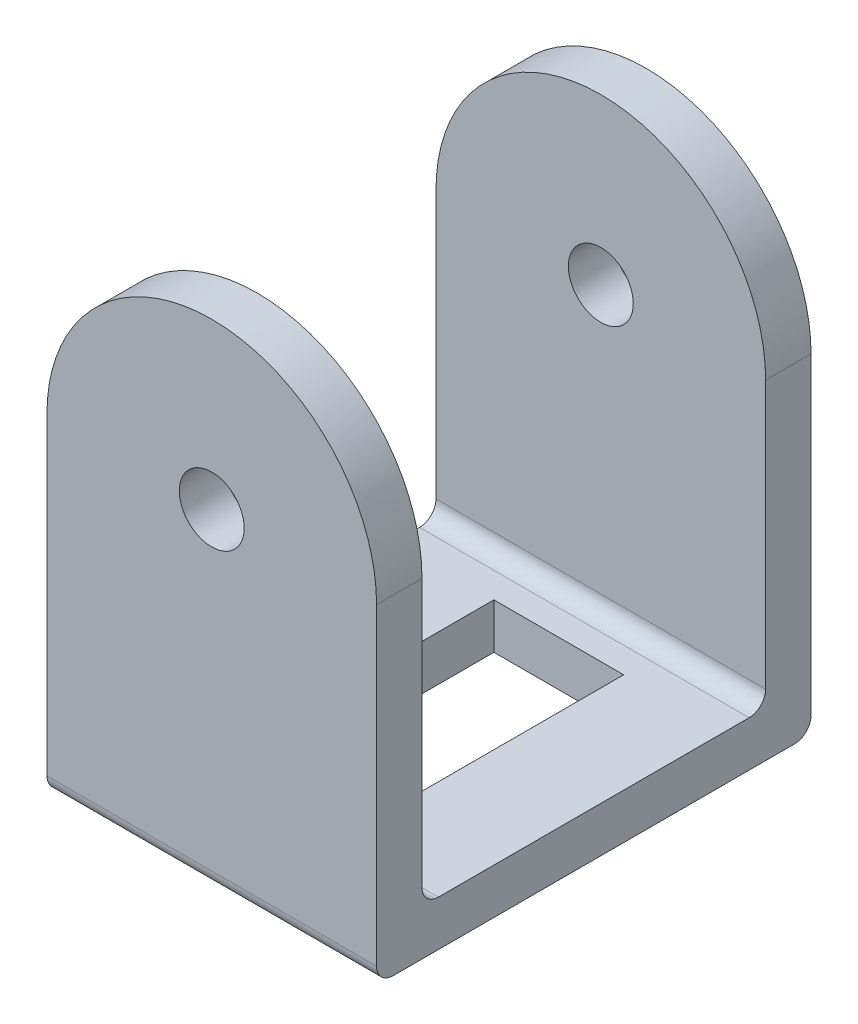
SolidWorks part; units mm, degrees
material "PBT General Purpose"
ref_plane "Front Plane" through (0, 0, 0) normal (0, 0, 1) x (1, 0, 0)
ref_plane "Top Plane" through (0, 0, 0) normal (0, 1, 0) x (1, 0, 0)
ref_plane "Right Plane" through (0, 0, 0) normal (1, 0, 0) x (0, 0, -1)
sketch "Sketch1" plane through (0, 0, 0) normal (0, 1, 0) x (1, 0, 0)
  line L1 (25.4, -33.48) -> (-25.4, -33.48)
  line L2 (25.4, -33.48) -> (25.4, 33.48)
  line L3 (25.4, 33.48) -> (-25.4, 33.48)
  line L4 (-25.4, -33.48) -> (-25.4, 33.48)
  line L5 (25.4, -33.48) -> (-25.4, 33.48) construction
  line L6 (25.4, 33.48) -> (-25.4, -33.48) construction
  point P0 (0, 0)
  dimension "D1" = 50.8
  dimension "D2" = 66.96
extrude "Boss-Extrude1" add sketch "Sketch1" along normal blind 7
sketch "Sketch2" plane through (0, 7, 0) normal (0, 1, 0) x (1, 0, 0)
  line L1 (10, -20) -> (-10, -20)
  line L2 (10, -20) -> (10, 20)
  line L3 (10, 20) -> (-10, 20)
  line L4 (-10, -20) -> (-10, 20)
  line L5 (10, -20) -> (-10, 20) construction
  line L6 (10, 20) -> (-10, -20) construction
  point P0 (0, 0)
  dimension "D1" = 20
  dimension "D2" = 40
extrude "Cut-Extrude1" cut sketch "Sketch2" against normal blind 7
sketch "Sketch3" plane through (0, 7, 0) normal (0, 1, 0) x (1, 0, 0)
  line L0 (25.4, -33.48) -> (25.4, 33.48) construction
  line L1 (-25.4, 33.48) -> (25.4, 33.48)
  line L2 (-25.4, 33.48) -> (-25.4, 26.48)
  line L3 (-25.4, 26.48) -> (25.4, 26.48)
  line L4 (25.4, 33.48) -> (25.4, 26.48)
  line L5 (-25.4, 33.48) -> (-25.4, -33.48) construction
  line L6 (25.4, -33.48) -> (-25.4, -33.48)
  line L7 (25.4, -33.48) -> (25.4, -26.48)
  line L8 (25.4, -26.48) -> (-25.4, -26.48)
  line L9 (-25.4, -33.48) -> (-25.4, -26.48)
  dimension "D1" = 7
  dimension "D2" = 7
extrude "Boss-Extrude2" add sketch "Sketch3" along normal blind 69.2
fillet "Fillet2" 2 edges at (-25.4, 76.2, -29.98) (25.4, 76.2, -29.98) type full round first side face at (-25.4, 39.85, 0) second side face at (25.4, 39.85, 0) middle face at (0, 76.2, -29.98)
fillet "Fillet3" 2 edges at (-25.4, 76.2, 29.98) (25.4, 76.2, 29.98) type full round first side face at (-25.4, 33.5, 0) second side face at (25.4, 33.5, 0) middle face at (0, 76.2, 29.98)
sketch "Sketch4" plane through (0, 0, -26.48) normal (0, 0, 1) x (1, 0, 0)
  line L0 (0, 7) -> (0, 50.8) construction
  line L1 (-25.4, 7) -> (25.4, 7) construction
  circle A0 centre (0, 50.8) radius 5
  dimension "D2" = 10
  dimension "D1" = 43.8
extrude "Cut-Extrude2" cut sketch "Sketch4" against normal mid plane 800
fillet "Fillet5" radius 2.54 4 edges at (0, 7, 26.48) (0, 0, -33.48) (0, 0, 33.48) (0, 7, -26.48)
